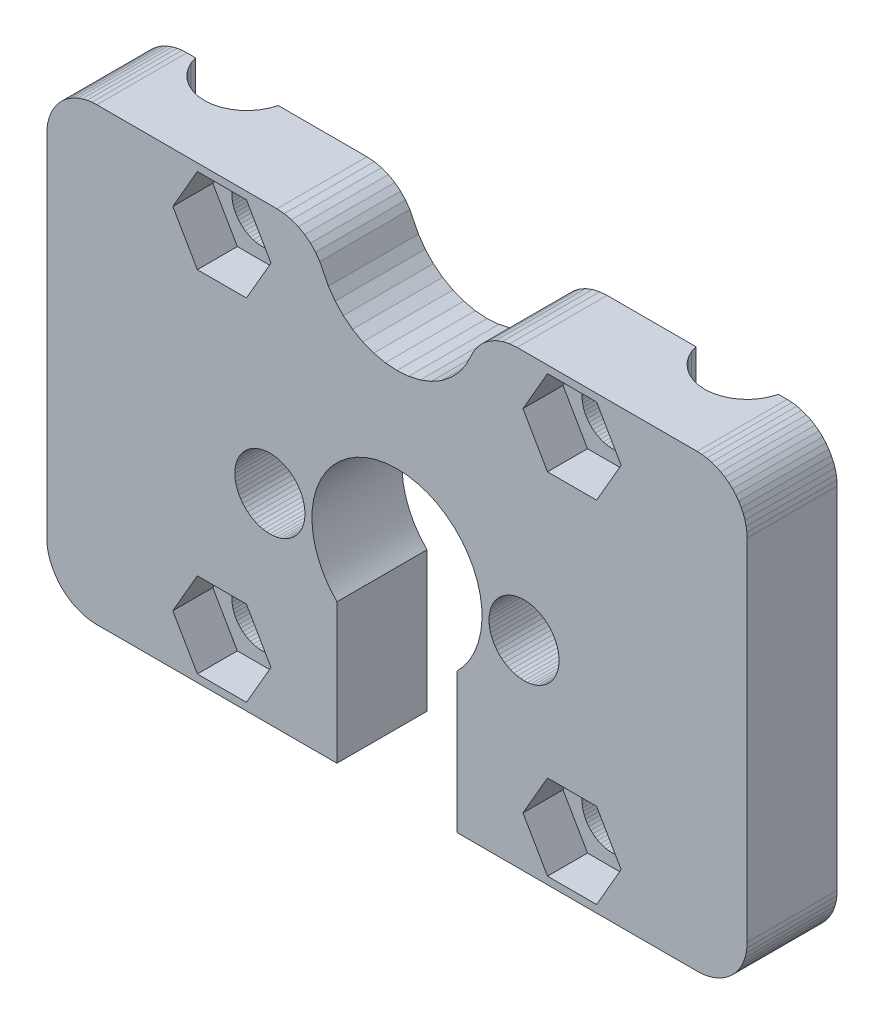
SolidWorks part; units mm, degrees
ref_plane "Front Plane" through (0, 0, 0) normal (0, 0, 1) x (1, 0, 0)
ref_plane "Top Plane" through (0, 0, 0) normal (0, 1, 0) x (1, 0, 0)
ref_plane "Right Plane" through (0, 0, 0) normal (1, 0, 0) x (0, 0, -1)
ref_plane "Plane1" through (0, 0, 9) normal (0, 0, 1) x (1, 0, 0)
sketch "Sketch1" plane through (0, 0, 9) normal (0, 0, 1) x (1, 0, 0)
  line L0 (5, 0) -> (65, 0)
  line L1 (65, 0) -> (65.4901, 0.0241)
  line L2 (65.4901, 0.0241) -> (65.9754, 0.0961)
  line L3 (65.9754, 0.0961) -> (66.4514, 0.2153)
  line L4 (66.4514, 0.2153) -> (66.9134, 0.3806)
  line L5 (66.9134, 0.3806) -> (67.357, 0.5904)
  line L6 (67.357, 0.5904) -> (67.7779, 0.8427)
  line L7 (67.7779, 0.8427) -> (68.172, 1.1349)
  line L8 (68.172, 1.1349) -> (68.5355, 1.4645)
  line L9 (68.5355, 1.4645) -> (68.865, 1.828)
  line L10 (68.865, 1.828) -> (69.1573, 2.2221)
  line L11 (69.1573, 2.2221) -> (69.4096, 2.643)
  line L12 (69.4096, 2.643) -> (69.6194, 3.0866)
  line L13 (69.6194, 3.0866) -> (69.7847, 3.5486)
  line L14 (69.7847, 3.5486) -> (69.9039, 4.0245)
  line L15 (69.9039, 4.0245) -> (69.9759, 4.5099)
  line L16 (69.9759, 4.5099) -> (70, 5)
  line L17 (70, 5) -> (70, 40)
  line L18 (70, 40) -> (69.9759, 40.4901)
  line L19 (69.9759, 40.4901) -> (69.9039, 40.9755)
  line L20 (69.9039, 40.9755) -> (69.7847, 41.4514)
  line L21 (69.7847, 41.4514) -> (69.6194, 41.9134)
  line L22 (69.6194, 41.9134) -> (69.4096, 42.357)
  line L23 (69.4096, 42.357) -> (69.1573, 42.7779)
  line L24 (69.1573, 42.7779) -> (68.865, 43.172)
  line L25 (68.865, 43.172) -> (68.5355, 43.5355)
  line L26 (68.5355, 43.5355) -> (68.172, 43.865)
  line L27 (68.172, 43.865) -> (67.7779, 44.1574)
  line L28 (67.7779, 44.1574) -> (67.357, 44.4096)
  line L29 (67.357, 44.4096) -> (66.9134, 44.6194)
  line L30 (66.9134, 44.6194) -> (66.4514, 44.7847)
  line L31 (66.4514, 44.7847) -> (65.9754, 44.9039)
  line L32 (65.9754, 44.9039) -> (65.4901, 44.9759)
  line L33 (65.4901, 44.9759) -> (65, 45)
  line L34 (65, 45) -> (47, 45)
  line L35 (47, 45) -> (46.2677, 44.946)
  line L36 (46.2677, 44.946) -> (45.5511, 44.7854)
  line L37 (45.5511, 44.7854) -> (44.8658, 44.5216)
  line L38 (44.8658, 44.5216) -> (44.2265, 44.1602)
  line L39 (44.2265, 44.1602) -> (43.6471, 43.7091)
  line L40 (43.6471, 43.7091) -> (43.1399, 43.178)
  line L41 (43.1399, 43.178) -> (42.7161, 42.5783)
  line L42 (42.7161, 42.5783) -> (42.3846, 41.923)
  line L43 (42.3846, 41.923) -> (41.8543, 40.8746)
  line L44 (41.8543, 40.8746) -> (41.1761, 39.9151)
  line L45 (41.1761, 39.9151) -> (40.3647, 39.0653)
  line L46 (40.3647, 39.0653) -> (39.4376, 38.3436)
  line L47 (39.4376, 38.3436) -> (38.4148, 37.7654)
  line L48 (38.4148, 37.7654) -> (37.3183, 37.3432)
  line L49 (37.3183, 37.3432) -> (36.1718, 37.0863)
  line L50 (36.1718, 37.0863) -> (35, 37)
  line L51 (35, 37) -> (33.8282, 37.0863)
  line L52 (33.8282, 37.0863) -> (32.6817, 37.3432)
  line L53 (32.6817, 37.3432) -> (31.5852, 37.7654)
  line L54 (31.5852, 37.7654) -> (30.5624, 38.3436)
  line L55 (30.5624, 38.3436) -> (29.6353, 39.0654)
  line L56 (29.6353, 39.0654) -> (28.8239, 39.9152)
  line L57 (28.8239, 39.9152) -> (28.1457, 40.8746)
  line L58 (28.1457, 40.8746) -> (27.6154, 41.9231)
  line L59 (27.6154, 41.9231) -> (27.2839, 42.5784)
  line L60 (27.2839, 42.5784) -> (26.8601, 43.178)
  line L61 (26.8601, 43.178) -> (26.3529, 43.7091)
  line L62 (26.3529, 43.7091) -> (25.7735, 44.1602)
  line L63 (25.7735, 44.1602) -> (25.1342, 44.5216)
  line L64 (25.1342, 44.5216) -> (24.4489, 44.7855)
  line L65 (24.4489, 44.7855) -> (23.7324, 44.9461)
  line L66 (23.7324, 44.9461) -> (23, 45)
  line L67 (23, 45) -> (5, 45)
  line L68 (5, 45) -> (4.5099, 44.9759)
  line L69 (4.5099, 44.9759) -> (4.0245, 44.9039)
  line L70 (4.0245, 44.9039) -> (3.5486, 44.7847)
  line L71 (3.5486, 44.7847) -> (3.0866, 44.6194)
  line L72 (3.0866, 44.6194) -> (2.643, 44.4096)
  line L73 (2.643, 44.4096) -> (2.2221, 44.1574)
  line L74 (2.2221, 44.1574) -> (1.828, 43.865)
  line L75 (1.828, 43.865) -> (1.4645, 43.5355)
  line L76 (1.4645, 43.5355) -> (1.1349, 43.172)
  line L77 (1.1349, 43.172) -> (0.8427, 42.7779)
  line L78 (0.8427, 42.7779) -> (0.5904, 42.357)
  line L79 (0.5904, 42.357) -> (0.3806, 41.9134)
  line L80 (0.3806, 41.9134) -> (0.2153, 41.4514)
  line L81 (0.2153, 41.4514) -> (0.0961, 40.9755)
  line L82 (0.0961, 40.9755) -> (0.0241, 40.4901)
  line L83 (0.0241, 40.4901) -> (0, 40)
  line L84 (0, 40) -> (0, 5)
  line L85 (0, 5) -> (0.0241, 4.5099)
  line L86 (0.0241, 4.5099) -> (0.0961, 4.0245)
  line L87 (0.0961, 4.0245) -> (0.2153, 3.5486)
  line L88 (0.2153, 3.5486) -> (0.3806, 3.0866)
  line L89 (0.3806, 3.0866) -> (0.5904, 2.643)
  line L90 (0.5904, 2.643) -> (0.8427, 2.2221)
  line L91 (0.8427, 2.2221) -> (1.1349, 1.828)
  line L92 (1.1349, 1.828) -> (1.4645, 1.4645)
  line L93 (1.4645, 1.4645) -> (1.828, 1.1349)
  line L94 (1.828, 1.1349) -> (2.2221, 0.8427)
  line L95 (2.2221, 0.8427) -> (2.643, 0.5904)
  line L96 (2.643, 0.5904) -> (3.0866, 0.3806)
  line L97 (3.0866, 0.3806) -> (3.5486, 0.2153)
  line L98 (3.5486, 0.2153) -> (4.0245, 0.0961)
  line L99 (4.0245, 0.0961) -> (4.5099, 0.0241)
  line L100 (4.5099, 0.0241) -> (5, 0)
extrude "Boss-Extrude1" add sketch "Sketch1" against normal blind 9
sketch "Sketch2" plane through (0, 45, 0) normal (0, 1, 0) x (-1, 0, 0)
  line L0 (-64.1307, 0) -> (-55.8693, 0)
  line L1 (-55.8693, 0) -> (-55.8693, 0.2506)
  line L2 (-55.8693, 0.2506) -> (-56.4239, 1.2964)
  line L3 (-56.4239, 1.2964) -> (-56.8543, 1.8579)
  line L4 (-56.8543, 1.8579) -> (-57.372, 2.3401)
  line L5 (-57.372, 2.3401) -> (-57.9625, 2.7298)
  line L6 (-57.9625, 2.7298) -> (-58.6095, 3.0161)
  line L7 (-58.6095, 3.0161) -> (-59.295, 3.1911)
  line L8 (-59.295, 3.1911) -> (-60, 3.25)
  line L9 (-60, 3.25) -> (-60.705, 3.1911)
  line L10 (-60.705, 3.1911) -> (-61.3905, 3.0161)
  line L11 (-61.3905, 3.0161) -> (-62.0375, 2.7298)
  line L12 (-62.0375, 2.7298) -> (-62.628, 2.3401)
  line L13 (-62.628, 2.3401) -> (-63.1457, 1.8579)
  line L14 (-63.1457, 1.8579) -> (-63.5761, 1.2964)
  line L15 (-63.5761, 1.2964) -> (-64.1307, 0.2506)
  line L16 (-64.1307, 0.2506) -> (-64.1307, 0)
extrude "Cut-Extrude1" cut sketch "Sketch2" against normal through all
sketch "Sketch3" plane through (0, 45, 0) normal (0, 1, 0) x (-1, 0, 0)
  line L0 (-14.1307, 0) -> (-5.8693, 0)
  line L1 (-5.8693, 0) -> (-5.8693, 0.2505)
  line L2 (-5.8693, 0.2505) -> (-6.4238, 1.2964)
  line L3 (-6.4238, 1.2964) -> (-6.8544, 1.8579)
  line L4 (-6.8544, 1.8579) -> (-7.372, 2.3401)
  line L5 (-7.372, 2.3401) -> (-7.9625, 2.7298)
  line L6 (-7.9625, 2.7298) -> (-8.6095, 3.0161)
  line L7 (-8.6095, 3.0161) -> (-9.295, 3.1911)
  line L8 (-9.295, 3.1911) -> (-10, 3.25)
  line L9 (-10, 3.25) -> (-10.705, 3.1911)
  line L10 (-10.705, 3.1911) -> (-11.3905, 3.0161)
  line L11 (-11.3905, 3.0161) -> (-12.0375, 2.7298)
  line L12 (-12.0375, 2.7298) -> (-12.628, 2.3401)
  line L13 (-12.628, 2.3401) -> (-13.1456, 1.8579)
  line L14 (-13.1456, 1.8579) -> (-13.5761, 1.2964)
  line L15 (-13.5761, 1.2964) -> (-14.1307, 0.2506)
  line L16 (-14.1307, 0.2506) -> (-14.1307, 0)
extrude "Cut-Extrude2" cut sketch "Sketch3" against normal through all
sketch "Sketch4" plane through (0, 0, 0) normal (0, 0, -1) x (-1, 0, 0)
  line L0 (-41, 0) -> (-29, 0)
  line L1 (-29, 0) -> (-29, 20)
  line L2 (-29, 20) -> (-29.0289, 20.5881)
  line L3 (-29.0289, 20.5881) -> (-29.1153, 21.1705)
  line L4 (-29.1153, 21.1705) -> (-29.2584, 21.7417)
  line L5 (-29.2584, 21.7417) -> (-29.4567, 22.2961)
  line L6 (-29.4567, 22.2961) -> (-29.7085, 22.8284)
  line L7 (-29.7085, 22.8284) -> (-30.0112, 23.3334)
  line L8 (-30.0112, 23.3334) -> (-30.3619, 23.8064)
  line L9 (-30.3619, 23.8064) -> (-30.7574, 24.2426)
  line L10 (-30.7574, 24.2426) -> (-31.1936, 24.6381)
  line L11 (-31.1936, 24.6381) -> (-31.6666, 24.9888)
  line L12 (-31.6666, 24.9888) -> (-32.1716, 25.2915)
  line L13 (-32.1716, 25.2915) -> (-32.7039, 25.5433)
  line L14 (-32.7039, 25.5433) -> (-33.2583, 25.7416)
  line L15 (-33.2583, 25.7416) -> (-33.8295, 25.8847)
  line L16 (-33.8295, 25.8847) -> (-34.4119, 25.9711)
  line L17 (-34.4119, 25.9711) -> (-35, 26)
  line L18 (-35, 26) -> (-35.5881, 25.9711)
  line L19 (-35.5881, 25.9711) -> (-36.1705, 25.8847)
  line L20 (-36.1705, 25.8847) -> (-36.7417, 25.7416)
  line L21 (-36.7417, 25.7416) -> (-37.2961, 25.5433)
  line L22 (-37.2961, 25.5433) -> (-37.8284, 25.2915)
  line L23 (-37.8284, 25.2915) -> (-38.3334, 24.9888)
  line L24 (-38.3334, 24.9888) -> (-38.8064, 24.6381)
  line L25 (-38.8064, 24.6381) -> (-39.2426, 24.2426)
  line L26 (-39.2426, 24.2426) -> (-39.6381, 23.8064)
  line L27 (-39.6381, 23.8064) -> (-39.9888, 23.3334)
  line L28 (-39.9888, 23.3334) -> (-40.2915, 22.8284)
  line L29 (-40.2915, 22.8284) -> (-40.5433, 22.2961)
  line L30 (-40.5433, 22.2961) -> (-40.7416, 21.7417)
  line L31 (-40.7416, 21.7417) -> (-40.8847, 21.1705)
  line L32 (-40.8847, 21.1705) -> (-40.9711, 20.5881)
  line L33 (-40.9711, 20.5881) -> (-41, 20)
  line L34 (-41, 20) -> (-41, 0)
extrude "Cut-Extrude3" cut sketch "Sketch4" against normal through all
sketch "Sketch5" plane through (0, 0, 9) normal (0, 0, 1) x (1, 0, 0)
  line L0 (54.9537, 9.25) -> (50.0463, 9.25)
  line L1 (50.0463, 9.25) -> (47.5925, 5)
  line L2 (47.5925, 5) -> (50.0463, 0.75)
  line L3 (50.0463, 0.75) -> (54.9537, 0.75)
  line L4 (54.9537, 0.75) -> (57.4075, 5)
  line L5 (57.4075, 5) -> (54.9537, 9.25)
extrude "Cut-Extrude4" cut sketch "Sketch5" against normal blind 4
sketch "Sketch6" plane through (0, 0, 0) normal (0, 0, -1) x (-1, 0, 0)
  line L0 (-49.5, 5) -> (-49.5144, 5.2941)
  line L1 (-49.5144, 5.2941) -> (-49.5576, 5.5853)
  line L2 (-49.5576, 5.5853) -> (-49.6292, 5.8709)
  line L3 (-49.6292, 5.8709) -> (-49.7284, 6.148)
  line L4 (-49.7284, 6.148) -> (-49.8542, 6.4142)
  line L5 (-49.8542, 6.4142) -> (-50.0056, 6.6667)
  line L6 (-50.0056, 6.6667) -> (-50.181, 6.9032)
  line L7 (-50.181, 6.9032) -> (-50.3787, 7.1213)
  line L8 (-50.3787, 7.1213) -> (-50.5968, 7.319)
  line L9 (-50.5968, 7.319) -> (-50.8333, 7.4944)
  line L10 (-50.8333, 7.4944) -> (-51.0858, 7.6458)
  line L11 (-51.0858, 7.6458) -> (-51.352, 7.7716)
  line L12 (-51.352, 7.7716) -> (-51.6292, 7.8708)
  line L13 (-51.6292, 7.8708) -> (-51.9147, 7.9424)
  line L14 (-51.9147, 7.9424) -> (-52.206, 7.9856)
  line L15 (-52.206, 7.9856) -> (-52.5, 8)
  line L16 (-52.5, 8) -> (-52.794, 7.9856)
  line L17 (-52.794, 7.9856) -> (-53.0853, 7.9424)
  line L18 (-53.0853, 7.9424) -> (-53.3708, 7.8708)
  line L19 (-53.3708, 7.8708) -> (-53.648, 7.7716)
  line L20 (-53.648, 7.7716) -> (-53.9142, 7.6458)
  line L21 (-53.9142, 7.6458) -> (-54.1667, 7.4944)
  line L22 (-54.1667, 7.4944) -> (-54.4032, 7.319)
  line L23 (-54.4032, 7.319) -> (-54.6213, 7.1213)
  line L24 (-54.6213, 7.1213) -> (-54.819, 6.9032)
  line L25 (-54.819, 6.9032) -> (-54.9944, 6.6667)
  line L26 (-54.9944, 6.6667) -> (-55.1458, 6.4142)
  line L27 (-55.1458, 6.4142) -> (-55.2716, 6.148)
  line L28 (-55.2716, 6.148) -> (-55.3708, 5.8709)
  line L29 (-55.3708, 5.8709) -> (-55.4424, 5.5853)
  line L30 (-55.4424, 5.5853) -> (-55.4856, 5.2941)
  line L31 (-55.4856, 5.2941) -> (-55.5, 5)
  line L32 (-55.5, 5) -> (-55.4856, 4.7059)
  line L33 (-55.4856, 4.7059) -> (-55.4424, 4.4147)
  line L34 (-55.4424, 4.4147) -> (-55.3708, 4.1291)
  line L35 (-55.3708, 4.1291) -> (-55.2716, 3.852)
  line L36 (-55.2716, 3.852) -> (-55.1458, 3.5858)
  line L37 (-55.1458, 3.5858) -> (-54.9944, 3.3333)
  line L38 (-54.9944, 3.3333) -> (-54.819, 3.0968)
  line L39 (-54.819, 3.0968) -> (-54.6213, 2.8787)
  line L40 (-54.6213, 2.8787) -> (-54.4032, 2.681)
  line L41 (-54.4032, 2.681) -> (-54.1667, 2.5056)
  line L42 (-54.1667, 2.5056) -> (-53.9142, 2.3542)
  line L43 (-53.9142, 2.3542) -> (-53.648, 2.2284)
  line L44 (-53.648, 2.2284) -> (-53.3708, 2.1292)
  line L45 (-53.3708, 2.1292) -> (-53.0853, 2.0576)
  line L46 (-53.0853, 2.0576) -> (-52.794, 2.0144)
  line L47 (-52.794, 2.0144) -> (-52.5, 2)
  line L48 (-52.5, 2) -> (-52.206, 2.0144)
  line L49 (-52.206, 2.0144) -> (-51.9147, 2.0576)
  line L50 (-51.9147, 2.0576) -> (-51.6292, 2.1292)
  line L51 (-51.6292, 2.1292) -> (-51.352, 2.2284)
  line L52 (-51.352, 2.2284) -> (-51.0858, 2.3542)
  line L53 (-51.0858, 2.3542) -> (-50.8333, 2.5056)
  line L54 (-50.8333, 2.5056) -> (-50.5968, 2.681)
  line L55 (-50.5968, 2.681) -> (-50.3787, 2.8787)
  line L56 (-50.3787, 2.8787) -> (-50.181, 3.0968)
  line L57 (-50.181, 3.0968) -> (-50.0056, 3.3333)
  line L58 (-50.0056, 3.3333) -> (-49.8542, 3.5858)
  line L59 (-49.8542, 3.5858) -> (-49.7284, 3.852)
  line L60 (-49.7284, 3.852) -> (-49.6292, 4.1291)
  line L61 (-49.6292, 4.1291) -> (-49.5576, 4.4147)
  line L62 (-49.5576, 4.4147) -> (-49.5144, 4.7059)
  line L63 (-49.5144, 4.7059) -> (-49.5, 5)
extrude "Cut-Extrude5" cut sketch "Sketch6" against normal through all
sketch "Sketch7" plane through (0, 0, 9) normal (0, 0, 1) x (1, 0, 0)
  line L0 (50.0463, 35.75) -> (54.9537, 35.75)
  line L1 (54.9537, 35.75) -> (57.4075, 40)
  line L2 (57.4075, 40) -> (54.9537, 44.25)
  line L3 (54.9537, 44.25) -> (50.0463, 44.25)
  line L4 (50.0463, 44.25) -> (47.5925, 40)
  line L5 (47.5925, 40) -> (50.0463, 35.75)
extrude "Cut-Extrude6" cut sketch "Sketch7" against normal blind 4
sketch "Sketch8" plane through (0, 0, 0) normal (0, 0, -1) x (-1, 0, 0)
  line L0 (-55.5, 40) -> (-55.4856, 39.706)
  line L1 (-55.4856, 39.706) -> (-55.4424, 39.4147)
  line L2 (-55.4424, 39.4147) -> (-55.3708, 39.1292)
  line L3 (-55.3708, 39.1292) -> (-55.2716, 38.852)
  line L4 (-55.2716, 38.852) -> (-55.1458, 38.5858)
  line L5 (-55.1458, 38.5858) -> (-54.9944, 38.3333)
  line L6 (-54.9944, 38.3333) -> (-54.819, 38.0968)
  line L7 (-54.819, 38.0968) -> (-54.6213, 37.8787)
  line L8 (-54.6213, 37.8787) -> (-54.4032, 37.681)
  line L9 (-54.4032, 37.681) -> (-54.1667, 37.5056)
  line L10 (-54.1667, 37.5056) -> (-53.9142, 37.3542)
  line L11 (-53.9142, 37.3542) -> (-53.648, 37.2284)
  line L12 (-53.648, 37.2284) -> (-53.3708, 37.1292)
  line L13 (-53.3708, 37.1292) -> (-53.0853, 37.0576)
  line L14 (-53.0853, 37.0576) -> (-52.794, 37.0144)
  line L15 (-52.794, 37.0144) -> (-52.5, 37)
  line L16 (-52.5, 37) -> (-52.206, 37.0145)
  line L17 (-52.206, 37.0145) -> (-51.9147, 37.0576)
  line L18 (-51.9147, 37.0576) -> (-51.6292, 37.1292)
  line L19 (-51.6292, 37.1292) -> (-51.352, 37.2284)
  line L20 (-51.352, 37.2284) -> (-51.0858, 37.3542)
  line L21 (-51.0858, 37.3542) -> (-50.8333, 37.5056)
  line L22 (-50.8333, 37.5056) -> (-50.5968, 37.681)
  line L23 (-50.5968, 37.681) -> (-50.3787, 37.8787)
  line L24 (-50.3787, 37.8787) -> (-50.181, 38.0968)
  line L25 (-50.181, 38.0968) -> (-50.0056, 38.3333)
  line L26 (-50.0056, 38.3333) -> (-49.8542, 38.5858)
  line L27 (-49.8542, 38.5858) -> (-49.7284, 38.852)
  line L28 (-49.7284, 38.852) -> (-49.6292, 39.1292)
  line L29 (-49.6292, 39.1292) -> (-49.5576, 39.4147)
  line L30 (-49.5576, 39.4147) -> (-49.5144, 39.706)
  line L31 (-49.5144, 39.706) -> (-49.5, 40)
  line L32 (-49.5, 40) -> (-49.5144, 40.294)
  line L33 (-49.5144, 40.294) -> (-49.5576, 40.5853)
  line L34 (-49.5576, 40.5853) -> (-49.6292, 40.8708)
  line L35 (-49.6292, 40.8708) -> (-49.7284, 41.148)
  line L36 (-49.7284, 41.148) -> (-49.8542, 41.4142)
  line L37 (-49.8542, 41.4142) -> (-50.0056, 41.6667)
  line L38 (-50.0056, 41.6667) -> (-50.181, 41.9032)
  line L39 (-50.181, 41.9032) -> (-50.3787, 42.1213)
  line L40 (-50.3787, 42.1213) -> (-50.5968, 42.319)
  line L41 (-50.5968, 42.319) -> (-50.8333, 42.4944)
  line L42 (-50.8333, 42.4944) -> (-51.0858, 42.6458)
  line L43 (-51.0858, 42.6458) -> (-51.352, 42.7716)
  line L44 (-51.352, 42.7716) -> (-51.6292, 42.8708)
  line L45 (-51.6292, 42.8708) -> (-51.9147, 42.9424)
  line L46 (-51.9147, 42.9424) -> (-52.206, 42.9856)
  line L47 (-52.206, 42.9856) -> (-52.5, 43)
  line L48 (-52.5, 43) -> (-52.794, 42.9856)
  line L49 (-52.794, 42.9856) -> (-53.0853, 42.9424)
  line L50 (-53.0853, 42.9424) -> (-53.3708, 42.8708)
  line L51 (-53.3708, 42.8708) -> (-53.648, 42.7716)
  line L52 (-53.648, 42.7716) -> (-53.9142, 42.6458)
  line L53 (-53.9142, 42.6458) -> (-54.1667, 42.4944)
  line L54 (-54.1667, 42.4944) -> (-54.4032, 42.319)
  line L55 (-54.4032, 42.319) -> (-54.6213, 42.1213)
  line L56 (-54.6213, 42.1213) -> (-54.819, 41.9032)
  line L57 (-54.819, 41.9032) -> (-54.9944, 41.6667)
  line L58 (-54.9944, 41.6667) -> (-55.1458, 41.4142)
  line L59 (-55.1458, 41.4142) -> (-55.2716, 41.148)
  line L60 (-55.2716, 41.148) -> (-55.3708, 40.8708)
  line L61 (-55.3708, 40.8708) -> (-55.4424, 40.5853)
  line L62 (-55.4424, 40.5853) -> (-55.4856, 40.294)
  line L63 (-55.4856, 40.294) -> (-55.5, 40)
extrude "Cut-Extrude7" cut sketch "Sketch8" against normal through all
sketch "Sketch9" plane through (0, 0, 9) normal (0, 0, 1) x (1, 0, 0)
  line L0 (12.5925, 40) -> (15.0463, 35.75)
  line L1 (15.0463, 35.75) -> (19.9537, 35.75)
  line L2 (19.9537, 35.75) -> (22.4075, 40)
  line L3 (22.4075, 40) -> (19.9537, 44.25)
  line L4 (19.9537, 44.25) -> (15.0463, 44.25)
  line L5 (15.0463, 44.25) -> (12.5925, 40)
extrude "Cut-Extrude8" cut sketch "Sketch9" against normal blind 4
sketch "Sketch10" plane through (0, 0, 0) normal (0, 0, -1) x (-1, 0, 0)
  line L0 (-17.206, 37.0144) -> (-16.9147, 37.0576)
  line L1 (-16.9147, 37.0576) -> (-16.6291, 37.1292)
  line L2 (-16.6291, 37.1292) -> (-16.352, 37.2284)
  line L3 (-16.352, 37.2284) -> (-16.0858, 37.3542)
  line L4 (-16.0858, 37.3542) -> (-15.8333, 37.5056)
  line L5 (-15.8333, 37.5056) -> (-15.5968, 37.681)
  line L6 (-15.5968, 37.681) -> (-15.3787, 37.8787)
  line L7 (-15.3787, 37.8787) -> (-15.181, 38.0968)
  line L8 (-15.181, 38.0968) -> (-15.0056, 38.3333)
  line L9 (-15.0056, 38.3333) -> (-14.8542, 38.5858)
  line L10 (-14.8542, 38.5858) -> (-14.7284, 38.852)
  line L11 (-14.7284, 38.852) -> (-14.6292, 39.1292)
  line L12 (-14.6292, 39.1292) -> (-14.5576, 39.4147)
  line L13 (-14.5576, 39.4147) -> (-14.5145, 39.706)
  line L14 (-14.5145, 39.706) -> (-14.5, 40)
  line L15 (-14.5, 40) -> (-14.5145, 40.294)
  line L16 (-14.5145, 40.294) -> (-14.5576, 40.5853)
  line L17 (-14.5576, 40.5853) -> (-14.6292, 40.8708)
  line L18 (-14.6292, 40.8708) -> (-14.7284, 41.148)
  line L19 (-14.7284, 41.148) -> (-14.8542, 41.4142)
  line L20 (-14.8542, 41.4142) -> (-15.0056, 41.6667)
  line L21 (-15.0056, 41.6667) -> (-15.181, 41.9032)
  line L22 (-15.181, 41.9032) -> (-15.3787, 42.1213)
  line L23 (-15.3787, 42.1213) -> (-15.5968, 42.319)
  line L24 (-15.5968, 42.319) -> (-15.8333, 42.4944)
  line L25 (-15.8333, 42.4944) -> (-16.0858, 42.6458)
  line L26 (-16.0858, 42.6458) -> (-16.352, 42.7716)
  line L27 (-16.352, 42.7716) -> (-16.6291, 42.8708)
  line L28 (-16.6291, 42.8708) -> (-16.9147, 42.9424)
  line L29 (-16.9147, 42.9424) -> (-17.206, 42.9856)
  line L30 (-17.206, 42.9856) -> (-17.5, 43)
  line L31 (-17.5, 43) -> (-17.794, 42.9856)
  line L32 (-17.794, 42.9856) -> (-18.0853, 42.9424)
  line L33 (-18.0853, 42.9424) -> (-18.3709, 42.8708)
  line L34 (-18.3709, 42.8708) -> (-18.6481, 42.7716)
  line L35 (-18.6481, 42.7716) -> (-18.9142, 42.6458)
  line L36 (-18.9142, 42.6458) -> (-19.1667, 42.4944)
  line L37 (-19.1667, 42.4944) -> (-19.4032, 42.319)
  line L38 (-19.4032, 42.319) -> (-19.6213, 42.1213)
  line L39 (-19.6213, 42.1213) -> (-19.819, 41.9032)
  line L40 (-19.819, 41.9032) -> (-19.9944, 41.6667)
  line L41 (-19.9944, 41.6667) -> (-20.1458, 41.4142)
  line L42 (-20.1458, 41.4142) -> (-20.2716, 41.148)
  line L43 (-20.2716, 41.148) -> (-20.3708, 40.8708)
  line L44 (-20.3708, 40.8708) -> (-20.4424, 40.5853)
  line L45 (-20.4424, 40.5853) -> (-20.4855, 40.294)
  line L46 (-20.4855, 40.294) -> (-20.5, 40)
  line L47 (-20.5, 40) -> (-20.4855, 39.706)
  line L48 (-20.4855, 39.706) -> (-20.4424, 39.4147)
  line L49 (-20.4424, 39.4147) -> (-20.3708, 39.1292)
  line L50 (-20.3708, 39.1292) -> (-20.2716, 38.852)
  line L51 (-20.2716, 38.852) -> (-20.1458, 38.5858)
  line L52 (-20.1458, 38.5858) -> (-19.9944, 38.3333)
  line L53 (-19.9944, 38.3333) -> (-19.819, 38.0968)
  line L54 (-19.819, 38.0968) -> (-19.6213, 37.8787)
  line L55 (-19.6213, 37.8787) -> (-19.4032, 37.681)
  line L56 (-19.4032, 37.681) -> (-19.1667, 37.5056)
  line L57 (-19.1667, 37.5056) -> (-18.9142, 37.3542)
  line L58 (-18.9142, 37.3542) -> (-18.648, 37.2284)
  line L59 (-18.648, 37.2284) -> (-18.3709, 37.1292)
  line L60 (-18.3709, 37.1292) -> (-18.0853, 37.0576)
  line L61 (-18.0853, 37.0576) -> (-17.794, 37.0144)
  line L62 (-17.794, 37.0144) -> (-17.5, 37)
  line L63 (-17.5, 37) -> (-17.206, 37.0144)
extrude "Cut-Extrude9" cut sketch "Sketch10" against normal through all
sketch "Sketch11" plane through (0, 0, 9) normal (0, 0, 1) x (1, 0, 0)
  line L0 (22.4075, 5) -> (19.9537, 9.25)
  line L1 (19.9537, 9.25) -> (15.0463, 9.25)
  line L2 (15.0463, 9.25) -> (12.5925, 5)
  line L3 (12.5925, 5) -> (15.0463, 0.75)
  line L4 (15.0463, 0.75) -> (19.9537, 0.75)
  line L5 (19.9537, 0.75) -> (22.4075, 5)
extrude "Cut-Extrude10" cut sketch "Sketch11" against normal blind 4
sketch "Sketch12" plane through (0, 0, 0) normal (0, 0, -1) x (-1, 0, 0)
  line L0 (-14.8542, 6.4142) -> (-15.0056, 6.6667)
  line L1 (-15.0056, 6.6667) -> (-15.181, 6.9032)
  line L2 (-15.181, 6.9032) -> (-15.3787, 7.1213)
  line L3 (-15.3787, 7.1213) -> (-15.5968, 7.319)
  line L4 (-15.5968, 7.319) -> (-15.8333, 7.4944)
  line L5 (-15.8333, 7.4944) -> (-16.0858, 7.6458)
  line L6 (-16.0858, 7.6458) -> (-16.352, 7.7716)
  line L7 (-16.352, 7.7716) -> (-16.6291, 7.8708)
  line L8 (-16.6291, 7.8708) -> (-16.9147, 7.9424)
  line L9 (-16.9147, 7.9424) -> (-17.206, 7.9856)
  line L10 (-17.206, 7.9856) -> (-17.5, 8)
  line L11 (-17.5, 8) -> (-17.794, 7.9856)
  line L12 (-17.794, 7.9856) -> (-18.0853, 7.9424)
  line L13 (-18.0853, 7.9424) -> (-18.3709, 7.8708)
  line L14 (-18.3709, 7.8708) -> (-18.6481, 7.7716)
  line L15 (-18.6481, 7.7716) -> (-18.9142, 7.6458)
  line L16 (-18.9142, 7.6458) -> (-19.1667, 7.4944)
  line L17 (-19.1667, 7.4944) -> (-19.4032, 7.319)
  line L18 (-19.4032, 7.319) -> (-19.6213, 7.1213)
  line L19 (-19.6213, 7.1213) -> (-19.819, 6.9032)
  line L20 (-19.819, 6.9032) -> (-19.9944, 6.6667)
  line L21 (-19.9944, 6.6667) -> (-20.1458, 6.4142)
  line L22 (-20.1458, 6.4142) -> (-20.2716, 6.148)
  line L23 (-20.2716, 6.148) -> (-20.3708, 5.8709)
  line L24 (-20.3708, 5.8709) -> (-20.4424, 5.5853)
  line L25 (-20.4424, 5.5853) -> (-20.4855, 5.2941)
  line L26 (-20.4855, 5.2941) -> (-20.5, 5)
  line L27 (-20.5, 5) -> (-20.4855, 4.7059)
  line L28 (-20.4855, 4.7059) -> (-20.4424, 4.4147)
  line L29 (-20.4424, 4.4147) -> (-20.3708, 4.1291)
  line L30 (-20.3708, 4.1291) -> (-20.2716, 3.852)
  line L31 (-20.2716, 3.852) -> (-20.1458, 3.5858)
  line L32 (-20.1458, 3.5858) -> (-19.9944, 3.3333)
  line L33 (-19.9944, 3.3333) -> (-19.819, 3.0968)
  line L34 (-19.819, 3.0968) -> (-19.6213, 2.8787)
  line L35 (-19.6213, 2.8787) -> (-19.4032, 2.681)
  line L36 (-19.4032, 2.681) -> (-19.1667, 2.5056)
  line L37 (-19.1667, 2.5056) -> (-18.9142, 2.3542)
  line L38 (-18.9142, 2.3542) -> (-18.6481, 2.2284)
  line L39 (-18.6481, 2.2284) -> (-18.3709, 2.1292)
  line L40 (-18.3709, 2.1292) -> (-18.0853, 2.0576)
  line L41 (-18.0853, 2.0576) -> (-17.794, 2.0144)
  line L42 (-17.794, 2.0144) -> (-17.5, 2)
  line L43 (-17.5, 2) -> (-17.206, 2.0144)
  line L44 (-17.206, 2.0144) -> (-16.9147, 2.0576)
  line L45 (-16.9147, 2.0576) -> (-16.6291, 2.1292)
  line L46 (-16.6291, 2.1292) -> (-16.352, 2.2284)
  line L47 (-16.352, 2.2284) -> (-16.0858, 2.3542)
  line L48 (-16.0858, 2.3542) -> (-15.8333, 2.5056)
  line L49 (-15.8333, 2.5056) -> (-15.5968, 2.681)
  line L50 (-15.5968, 2.681) -> (-15.3787, 2.8787)
  line L51 (-15.3787, 2.8787) -> (-15.181, 3.0968)
  line L52 (-15.181, 3.0968) -> (-15.0056, 3.3333)
  line L53 (-15.0056, 3.3333) -> (-14.8542, 3.5858)
  line L54 (-14.8542, 3.5858) -> (-14.7284, 3.852)
  line L55 (-14.7284, 3.852) -> (-14.6292, 4.1291)
  line L56 (-14.6292, 4.1291) -> (-14.5576, 4.4147)
  line L57 (-14.5576, 4.4147) -> (-14.5145, 4.7059)
  line L58 (-14.5145, 4.7059) -> (-14.5, 5)
  line L59 (-14.5, 5) -> (-14.5145, 5.2941)
  line L60 (-14.5145, 5.2941) -> (-14.5576, 5.5853)
  line L61 (-14.5576, 5.5853) -> (-14.6292, 5.8709)
  line L62 (-14.6292, 5.8709) -> (-14.7284, 6.148)
  line L63 (-14.7284, 6.148) -> (-14.8542, 6.4142)
extrude "Cut-Extrude11" cut sketch "Sketch12" against normal through all
sketch "Sketch13" plane through (0, 0, 9) normal (0, 0, 1) x (1, 0, 0)
  line L0 (22.3, 23.5) -> (21.9569, 23.4831)
  line L1 (21.9569, 23.4831) -> (21.6172, 23.4327)
  line L2 (21.6172, 23.4327) -> (21.284, 23.3493)
  line L3 (21.284, 23.3493) -> (20.9606, 23.2336)
  line L4 (20.9606, 23.2336) -> (20.6501, 23.0867)
  line L5 (20.6501, 23.0867) -> (20.3555, 22.9101)
  line L6 (20.3555, 22.9101) -> (20.0796, 22.7055)
  line L7 (20.0796, 22.7055) -> (19.8251, 22.4749)
  line L8 (19.8251, 22.4749) -> (19.5945, 22.2204)
  line L9 (19.5945, 22.2204) -> (19.3899, 21.9445)
  line L10 (19.3899, 21.9445) -> (19.2133, 21.6499)
  line L11 (19.2133, 21.6499) -> (19.0664, 21.3394)
  line L12 (19.0664, 21.3394) -> (18.9507, 21.016)
  line L13 (18.9507, 21.016) -> (18.8672, 20.6828)
  line L14 (18.8672, 20.6828) -> (18.8168, 20.3431)
  line L15 (18.8168, 20.3431) -> (18.8, 20)
  line L16 (18.8, 20) -> (18.8168, 19.6569)
  line L17 (18.8168, 19.6569) -> (18.8672, 19.3172)
  line L18 (18.8672, 19.3172) -> (18.9507, 18.984)
  line L19 (18.9507, 18.984) -> (19.0664, 18.6606)
  line L20 (19.0664, 18.6606) -> (19.2133, 18.3501)
  line L21 (19.2133, 18.3501) -> (19.3899, 18.0555)
  line L22 (19.3899, 18.0555) -> (19.5945, 17.7796)
  line L23 (19.5945, 17.7796) -> (19.8251, 17.5251)
  line L24 (19.8251, 17.5251) -> (20.0796, 17.2945)
  line L25 (20.0796, 17.2945) -> (20.3555, 17.0899)
  line L26 (20.3555, 17.0899) -> (20.6501, 16.9133)
  line L27 (20.6501, 16.9133) -> (20.9606, 16.7664)
  line L28 (20.9606, 16.7664) -> (21.284, 16.6507)
  line L29 (21.284, 16.6507) -> (21.6172, 16.5673)
  line L30 (21.6172, 16.5673) -> (21.9569, 16.5169)
  line L31 (21.9569, 16.5169) -> (22.3, 16.5)
  line L32 (22.3, 16.5) -> (22.6431, 16.5169)
  line L33 (22.6431, 16.5169) -> (22.9828, 16.5673)
  line L34 (22.9828, 16.5673) -> (23.316, 16.6507)
  line L35 (23.316, 16.6507) -> (23.6394, 16.7664)
  line L36 (23.6394, 16.7664) -> (23.9499, 16.9133)
  line L37 (23.9499, 16.9133) -> (24.2445, 17.0899)
  line L38 (24.2445, 17.0899) -> (24.5204, 17.2945)
  line L39 (24.5204, 17.2945) -> (24.7749, 17.5251)
  line L40 (24.7749, 17.5251) -> (25.0055, 17.7796)
  line L41 (25.0055, 17.7796) -> (25.2101, 18.0555)
  line L42 (25.2101, 18.0555) -> (25.3867, 18.3501)
  line L43 (25.3867, 18.3501) -> (25.5336, 18.6606)
  line L44 (25.5336, 18.6606) -> (25.6493, 18.984)
  line L45 (25.6493, 18.984) -> (25.7327, 19.3172)
  line L46 (25.7327, 19.3172) -> (25.7832, 19.6569)
  line L47 (25.7832, 19.6569) -> (25.8, 20)
  line L48 (25.8, 20) -> (25.7832, 20.3431)
  line L49 (25.7832, 20.3431) -> (25.7327, 20.6828)
  line L50 (25.7327, 20.6828) -> (25.6493, 21.016)
  line L51 (25.6493, 21.016) -> (25.5336, 21.3394)
  line L52 (25.5336, 21.3394) -> (25.3867, 21.6499)
  line L53 (25.3867, 21.6499) -> (25.2101, 21.9445)
  line L54 (25.2101, 21.9445) -> (25.0055, 22.2204)
  line L55 (25.0055, 22.2204) -> (24.7749, 22.4749)
  line L56 (24.7749, 22.4749) -> (24.5204, 22.7055)
  line L57 (24.5204, 22.7055) -> (24.2445, 22.9101)
  line L58 (24.2445, 22.9101) -> (23.9499, 23.0867)
  line L59 (23.9499, 23.0867) -> (23.6394, 23.2336)
  line L60 (23.6394, 23.2336) -> (23.316, 23.3493)
  line L61 (23.316, 23.3493) -> (22.9828, 23.4327)
  line L62 (22.9828, 23.4327) -> (22.6431, 23.4831)
  line L63 (22.6431, 23.4831) -> (22.3, 23.5)
extrude "Cut-Extrude12" cut sketch "Sketch13" against normal through all
sketch "Sketch14" plane through (0, 0, 0) normal (0, 0, -1) x (-1, 0, 0)
  line L0 (-47.3569, 16.5169) -> (-47.0172, 16.5673)
  line L1 (-47.0172, 16.5673) -> (-46.684, 16.6507)
  line L2 (-46.684, 16.6507) -> (-46.3606, 16.7664)
  line L3 (-46.3606, 16.7664) -> (-46.0501, 16.9133)
  line L4 (-46.0501, 16.9133) -> (-45.7555, 17.0899)
  line L5 (-45.7555, 17.0899) -> (-45.4796, 17.2945)
  line L6 (-45.4796, 17.2945) -> (-45.2251, 17.5251)
  line L7 (-45.2251, 17.5251) -> (-44.9945, 17.7796)
  line L8 (-44.9945, 17.7796) -> (-44.7899, 18.0555)
  line L9 (-44.7899, 18.0555) -> (-44.6133, 18.3501)
  line L10 (-44.6133, 18.3501) -> (-44.4664, 18.6606)
  line L11 (-44.4664, 18.6606) -> (-44.3507, 18.984)
  line L12 (-44.3507, 18.984) -> (-44.2673, 19.3172)
  line L13 (-44.2673, 19.3172) -> (-44.2169, 19.6569)
  line L14 (-44.2169, 19.6569) -> (-44.2, 20)
  line L15 (-44.2, 20) -> (-44.2169, 20.3431)
  line L16 (-44.2169, 20.3431) -> (-44.2673, 20.6828)
  line L17 (-44.2673, 20.6828) -> (-44.3507, 21.016)
  line L18 (-44.3507, 21.016) -> (-44.4664, 21.3394)
  line L19 (-44.4664, 21.3394) -> (-44.6133, 21.6499)
  line L20 (-44.6133, 21.6499) -> (-44.7899, 21.9445)
  line L21 (-44.7899, 21.9445) -> (-44.9945, 22.2204)
  line L22 (-44.9945, 22.2204) -> (-45.2251, 22.4749)
  line L23 (-45.2251, 22.4749) -> (-45.4796, 22.7055)
  line L24 (-45.4796, 22.7055) -> (-45.7555, 22.9101)
  line L25 (-45.7555, 22.9101) -> (-46.0501, 23.0867)
  line L26 (-46.0501, 23.0867) -> (-46.3606, 23.2336)
  line L27 (-46.3606, 23.2336) -> (-46.684, 23.3493)
  line L28 (-46.684, 23.3493) -> (-47.0172, 23.4327)
  line L29 (-47.0172, 23.4327) -> (-47.3569, 23.4831)
  line L30 (-47.3569, 23.4831) -> (-47.7, 23.5)
  line L31 (-47.7, 23.5) -> (-48.0431, 23.4831)
  line L32 (-48.0431, 23.4831) -> (-48.3828, 23.4327)
  line L33 (-48.3828, 23.4327) -> (-48.716, 23.3493)
  line L34 (-48.716, 23.3493) -> (-49.0394, 23.2336)
  line L35 (-49.0394, 23.2336) -> (-49.3499, 23.0867)
  line L36 (-49.3499, 23.0867) -> (-49.6445, 22.9101)
  line L37 (-49.6445, 22.9101) -> (-49.9204, 22.7055)
  line L38 (-49.9204, 22.7055) -> (-50.1749, 22.4749)
  line L39 (-50.1749, 22.4749) -> (-50.4055, 22.2204)
  line L40 (-50.4055, 22.2204) -> (-50.6101, 21.9445)
  line L41 (-50.6101, 21.9445) -> (-50.7867, 21.6499)
  line L42 (-50.7867, 21.6499) -> (-50.9336, 21.3394)
  line L43 (-50.9336, 21.3394) -> (-51.0493, 21.016)
  line L44 (-51.0493, 21.016) -> (-51.1328, 20.6828)
  line L45 (-51.1328, 20.6828) -> (-51.1831, 20.3431)
  line L46 (-51.1831, 20.3431) -> (-51.2, 20)
  line L47 (-51.2, 20) -> (-51.1831, 19.6569)
  line L48 (-51.1831, 19.6569) -> (-51.1328, 19.3172)
  line L49 (-51.1328, 19.3172) -> (-51.0493, 18.984)
  line L50 (-51.0493, 18.984) -> (-50.9336, 18.6606)
  line L51 (-50.9336, 18.6606) -> (-50.7867, 18.3501)
  line L52 (-50.7867, 18.3501) -> (-50.6101, 18.0555)
  line L53 (-50.6101, 18.0555) -> (-50.4055, 17.7796)
  line L54 (-50.4055, 17.7796) -> (-50.1749, 17.5251)
  line L55 (-50.1749, 17.5251) -> (-49.9204, 17.2945)
  line L56 (-49.9204, 17.2945) -> (-49.6445, 17.0899)
  line L57 (-49.6445, 17.0899) -> (-49.3499, 16.9133)
  line L58 (-49.3499, 16.9133) -> (-49.0394, 16.7664)
  line L59 (-49.0394, 16.7664) -> (-48.716, 16.6507)
  line L60 (-48.716, 16.6507) -> (-48.3828, 16.5673)
  line L61 (-48.3828, 16.5673) -> (-48.0431, 16.5169)
  line L62 (-48.0431, 16.5169) -> (-47.7, 16.5)
  line L63 (-47.7, 16.5) -> (-47.3569, 16.5169)
extrude "Cut-Extrude13" cut sketch "Sketch14" against normal through all
draft "Draft1" type of draft neutral plane draft angle 18.383 faces to draft 1 face at (5.8693, 22.5, 0.1253) neutral plane through (-1.9483, 0.3413, 0) neutral plane normal (0, 0, -1) parameters "D1"=18.383
draft "Draft2" type of draft neutral plane draft angle 18.383 faces to draft 1 face at (64.1307, 22.5, 0.1253) neutral plane through (-1.9483, 0.3413, 0) neutral plane normal (0, 0, -1) parameters "D1"=18.383
draft "Draft3" type of draft neutral plane draft angle 18.383 faces to draft 2 face at (55.8693, 22.5, 0.1253) face at (14.1307, 22.5, 0.1253) neutral plane through (-1.9483, 0.3413, 0) neutral plane normal (0, 0, -1) parameters "D1"=18.383
sketch "Sketch15" plane through (0, 0, 9) normal (0, 0, 1) x (1, 0, 0)
  circle A0 centre (35, 20) radius 8.5
  dimension "D1" = 17
extrude "Cut-Extrude14" cut sketch "Sketch15" against normal through all
